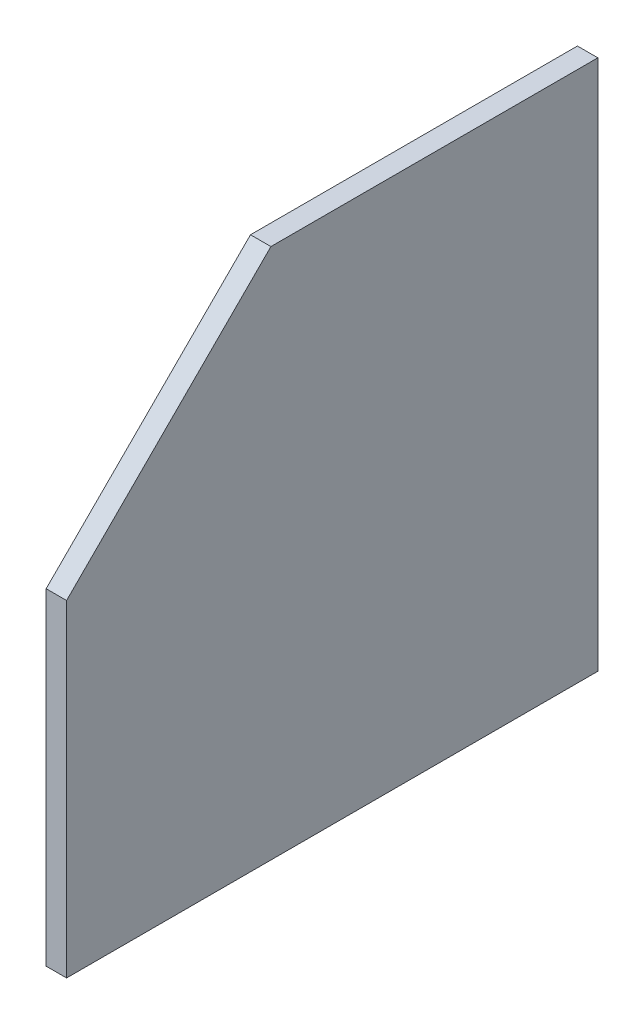
SolidWorks part; units mm, degrees
material "6061-T6 (SS)"
ref_plane "Front Plane" through (0, 0, 0) normal (0, 0, 1) x (1, 0, 0)
ref_plane "Top Plane" through (0, 0, 0) normal (0, 1, 0) x (1, 0, 0)
ref_plane "Right Plane" through (0, 0, 0) normal (1, 0, 0) x (0, 0, -1)
sketch "Sketch1" plane through (0, 0, 0) normal (1, 0, 0) x (0, 0, -1)
  line L0 (0, 0) -> (0, 82.55)
  line L1 (0, 82.55) -> (-50.8, 82.55)
  line L2 (-50.8, 82.55) -> (-82.55, 50.8)
  line L3 (-82.55, 50.8) -> (-82.55, 0)
  line L4 (-82.55, 0) -> (0, 0)
  dimension "D1" = 50.8
  dimension "D2" = 45
  dimension "D3" = 82.55
extrude "Boss-Extrude1" add sketch "Sketch1" along normal blind 3.175
